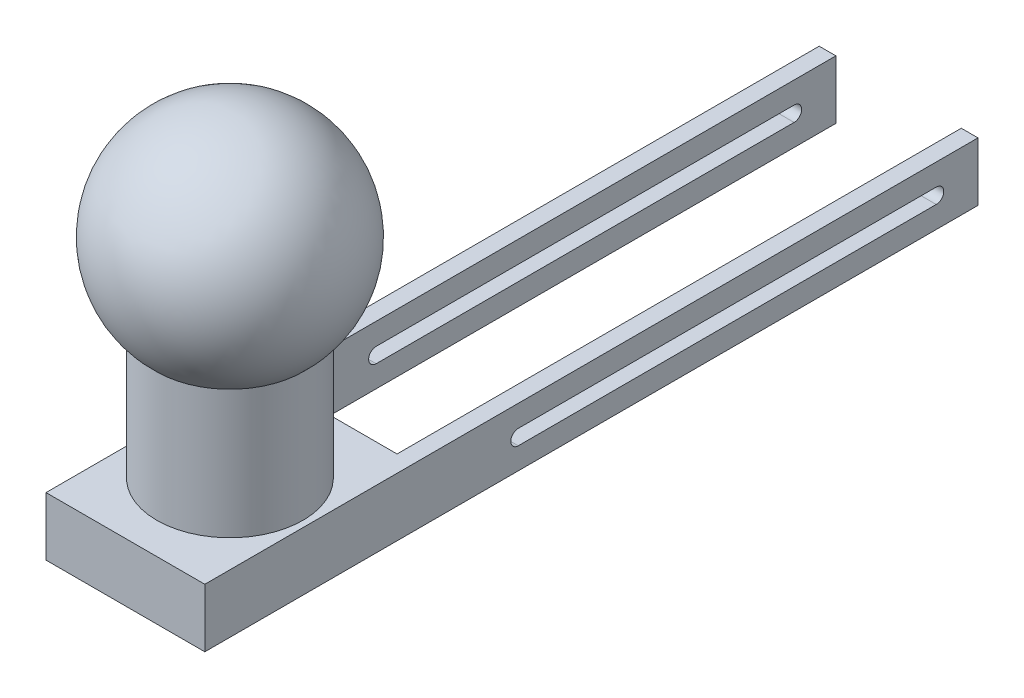
SolidWorks part; units mm, degrees
ref_plane "Front Plane" through (0, 0, 0) normal (0, 0, 1) x (1, 0, 0)
ref_plane "Top Plane" through (0, 0, 0) normal (0, 1, 0) x (1, 0, 0)
ref_plane "Right Plane" through (0, 0, 0) normal (1, 0, 0) x (0, 0, -1)
sketch "Sketch1" plane through (0, 0, 0) normal (0, 1, 0) x (1, 0, 0)
  line L0 (0, 0) -> (0, 88.1944) construction
  line L1 (-19.05, 112.8889) -> (-24.13, 112.8889)
  line L2 (-24.13, 112.8889) -> (-24.13, -122.0611)
  line L3 (-24.13, -122.0611) -> (24.13, -122.0611)
  line L4 (0, -122.0611) -> (0, -58.5611) construction
  line L5 (19.05, -58.5611) -> (-19.05, -58.5611)
  line L6 (-19.05, -58.5611) -> (-19.05, 112.8889)
  line L7 (24.13, 112.8889) -> (24.13, -122.0611)
  line L8 (0, -90.3111) -> (-24.13, -90.3111) construction
  line L9 (19.05, -58.5611) -> (19.05, 112.8889)
  line L10 (19.05, 112.8889) -> (24.13, 112.8889)
  dimension "D1" = 5.08
  dimension "D2" = 19.05
  dimension "D3" = 203.2
  dimension "D4" = 63.5
extrude "Boss-Extrude1" add sketch "Sketch1" against normal blind 17.78
sketch "Sketch3" plane through (0, 0, 0) normal (0, 1, 0) x (1, 0, 0)
  line L0 (0, -58.5611) -> (0, -122.0611) construction
  line L1 (19.05, -58.5611) -> (-19.05, -58.5611) construction
  line L2 (-24.13, -122.0611) -> (24.13, -122.0611) construction
  line L3 (0, -90.3111) -> (-24.13, -90.3111) construction
  line L4 (-24.13, 112.8889) -> (-24.13, -122.0611) construction
  circle A0 centre (0, -90.3111) radius 22.225
  dimension "D1" = 44.45
extrude "Boss-Extrude2" add sketch "Sketch3" along normal blind 63.5
ref_axis "Axis1" through (0, 63.5, 90.3111) along (0, -1, 0)
ref_plane "Plane1" through (0, 0, 90.3111) normal (0, 0, 1) x (0, -1, 0)
sketch "Sketch5" plane through (0, 0, 90.3111) normal (0, 0, 1) x (0, -1, 0)
  line L0 (-63.5, 0) -> (-63.5, 33.02) construction
  line L1 (-63.5, 22.225) -> (-63.5, -22.225) construction
  line L2 (-63.5, -33.02) -> (-63.5, 33.02)
  arc A0 (-63.5, 33.02) -> (-63.5, -33.02) centre (-63.5, 0) ccw
  dimension "D1" = 33.02
revolve "Revolve1" add sketch "Sketch5" angle 360 about L0
sketch "Sketch6" plane through (-24.13, 0, 0) normal (-1, 0, 0) x (0, 0, 1)
  line L0 (-112.8889, -8.89) -> (122.0611, -8.89) construction
  line L1 (-112.8889, -17.78) -> (-112.8889, 0) construction
  line L2 (122.0611, -17.78) -> (122.0611, 0) construction
  line L3 (-100.1889, -8.89) -> (26.8111, -8.89) construction
  line L4 (-100.1889, -6.604) -> (26.8111, -6.604)
  line L5 (-100.1889, -11.176) -> (26.8111, -11.176)
  arc A0 (-100.1889, -6.604) -> (-100.1889, -11.176) centre (-100.1889, -8.89) ccw
  arc A1 (26.8111, -11.176) -> (26.8111, -6.604) centre (26.8111, -8.89) ccw
  point P8 (-36.6889, -8.89)
  dimension "D1" = 4.572
  dimension "D2" = 12.7
  dimension "D3" = 127
extrude "Cut-Extrude1" cut sketch "Sketch6" against normal through all
